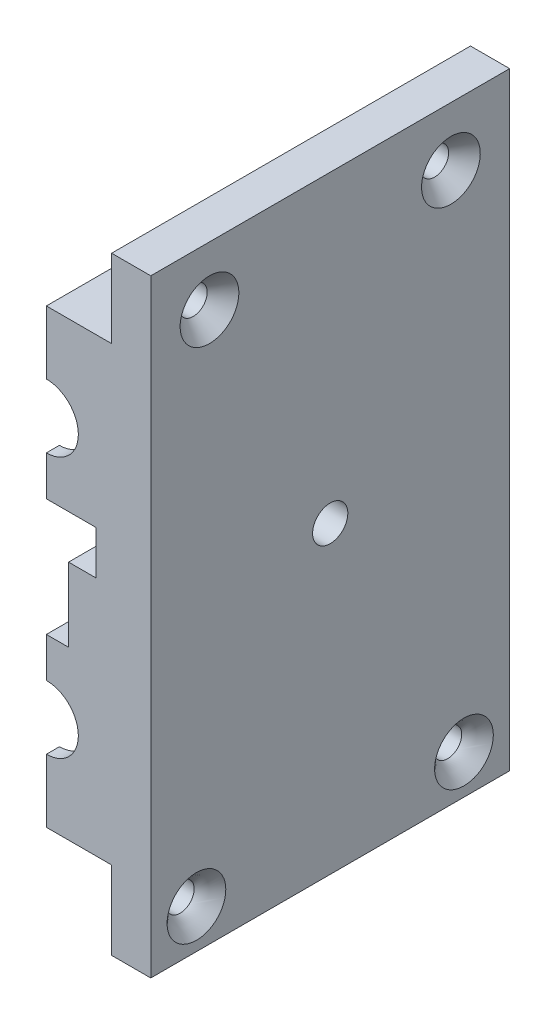
SolidWorks part; units mm, degrees
ref_plane "Front Plane" through (0, 0, 0) normal (0, 0, 1) x (1, 0, 0)
ref_plane "Top Plane" through (0, 0, 0) normal (0, 1, 0) x (1, 0, 0)
ref_plane "Right Plane" through (0, 0, 0) normal (1, 0, 0) x (0, 0, -1)
sketch "Sketch1" plane through (0, 0, 0) normal (0, 0, 1) x (1, 0, 0)
  line L0 (0, 0) -> (0, -93.2)
  line L1 (0, -93.2) -> (-6, -93.2)
  line L2 (-6, -93.2) -> (-6, -81.2)
  line L3 (-6, -81.2) -> (-16, -81.2)
  line L4 (-16, -81.2) -> (-16, -74.2)
  line L5 (-16, -59) -> (-16, -44.3)
  line L6 (-16, -44.3) -> (-8.4, -44.3)
  line L7 (-8.4, -44.3) -> (-8.4, -37.6)
  line L8 (-8.4, -37.6) -> (-16, -37.6)
  line L9 (-16, -37.6) -> (-16, -34.2)
  line L10 (-16, -19) -> (-16, -12)
  line L11 (-16, -12) -> (-6, -12)
  line L12 (-6, -12) -> (-6, 0)
  line L13 (-6, 0) -> (0, 0)
  arc A0 (-16, -74.2) -> (-16, -59) centre (-16, -66.6) ccw
  arc A1 (-16, -34.2) -> (-16, -19) centre (-16, -26.6) ccw
  dimension "D6" = 7.6
  dimension "D7" = 7.6
  dimension "D1" = 6
  dimension "D2" = 12
  dimension "D3" = 12
  dimension "D4" = 14.7
  dimension "D5" = 40
  dimension "D8" = 7
  dimension "D9" = 3.4
  dimension "D11" = 10
  dimension "D12" = 10
extrude "Boss-Extrude1" add sketch "Sketch1" along normal blind 55
ref_plane "Plane1" through (0, 0, 28.5) normal (0, 0, -1) x (-1, 0, 0)
sketch "Sketch2" plane through (0, 0, 28.5) normal (0, 0, -1) x (-1, 0, 0)
  line L0 (16, -34.2) -> (16, -31.5)
  line L1 (16, -21.7) -> (16, -19)
  arc A0 (16, -19) -> (16, -34.2) centre (16, -26.6) ccw
  arc A1 (16, -21.7) -> (16, -31.5) centre (16, -26.6) ccw
  dimension "D1" = 4.9
extrude "Boss-Extrude2" add sketch "Sketch2" along normal blind 2
sketch "Sketch3" plane through (0, 0, 28.5) normal (0, 0, -1) x (-1, 0, 0)
  line L0 (16, -74.2) -> (16, -71.5)
  line L1 (16, -61.7) -> (16, -59)
  arc A0 (16, -59) -> (16, -74.2) centre (16, -66.6) ccw
  arc A1 (16, -61.7) -> (16, -71.5) centre (16, -66.6) ccw
  dimension "D1" = 4.9
extrude "Boss-Extrude3" add sketch "Sketch3" along normal blind 2
ref_plane "Plane2" through (0, 0, 2) normal (0, 0, -1) x (-1, 0, 0)
sketch "Sketch4" plane through (0, 0, 2) normal (0, 0, -1) x (-1, 0, 0)
  line L1 (16, -59) -> (16, -61.7)
  line L2 (16, -74.2) -> (16, -81.2) construction
  line L4 (16, -71.5) -> (16, -74.2)
  line L5 (16, -19) -> (16, -21.7)
  line L6 (16, -31.5) -> (16, -34.2)
  arc A1 (16, -59) -> (16, -74.2) centre (16, -66.6) ccw construction
  arc A2 (16, -74.2) -> (16, -59) centre (16, -66.6) cw
  arc A4 (16, -61.7) -> (16, -71.5) centre (16, -66.6) ccw
  arc A5 (16, -34.2) -> (16, -19) centre (16, -26.6) cw
  arc A6 (16, -21.7) -> (16, -31.5) centre (16, -26.6) ccw
  dimension "D1" = 4.9
  dimension "D2" = 4.9
extrude "Boss-Extrude5" add sketch "Sketch4" along normal blind 2
ref_plane "Plane3" through (0, 0, 53) normal (0, 0, -1) x (-1, 0, 0)
sketch "Sketch5" plane through (0, 0, 53) normal (0, 0, -1) x (-1, 0, 0)
  line L0 (16, -19) -> (16, -21.7)
  line L1 (16, -31.5) -> (16, -34.2)
  line L2 (16, -59) -> (16, -61.7)
  line L3 (16, -71.5) -> (16, -74.2)
  arc A0 (16, -19) -> (16, -34.2) centre (16, -26.6) ccw construction
  arc A1 (16, -34.2) -> (16, -19) centre (16, -26.6) cw
  arc A2 (16, -21.7) -> (16, -31.5) centre (16, -26.6) ccw
  arc A3 (16, -74.2) -> (16, -59) centre (16, -66.6) cw
  arc A4 (16, -61.7) -> (16, -71.5) centre (16, -66.6) ccw
  dimension "D1" = 4.9
extrude "Boss-Extrude6" add sketch "Sketch5" against normal blind 2
sketch "Sketch7" plane through (0, 0, 55) normal (0, 0, 1) x (1, 0, 0)
  line L1 (-16, -44.3) -> (-12.6, -44.3)
  line L2 (-16, -44.3) -> (-16, -55.6)
  line L3 (-16, -55.6) -> (-12.6, -55.6)
  line L4 (-12.6, -44.3) -> (-12.6, -55.6)
  dimension "D1" = 3.4
  dimension "D2" = 11.3
extrude "Cut-Extrude2" cut sketch "Sketch7" against normal up to surface (55 mm away) up to face at (-9.9375, -45.1875, 0)
sketch "Sketch8" plane through (0, 0, 0) normal (1, 0, 0) x (0, 0, -1)
  line L0 (-55, -93.2) -> (-55, 0) construction
  line L1 (0, -93.2) -> (0, 0) construction
  line L2 (-55, 0) -> (0, 0) construction
  line L3 (-55, -93.2) -> (0, -93.2) construction
  circle A0 centre (-46, -9) radius 2.15
  circle A1 centre (-9, -9) radius 2.15
  circle A2 centre (-7, -87.2) radius 2.15
  circle A3 centre (-48, -87.2) radius 2.15
  dimension "D1" = 4.3
  dimension "D2" = 4.3
  dimension "D3" = 4.3
  dimension "D4" = 4.3
  dimension "D5" = 9
  dimension "D6" = 9
  dimension "D7" = 7
  dimension "D8" = 7
  dimension "D9" = 9
  dimension "D10" = 9
  dimension "D11" = 6
  dimension "D12" = 6
extrude "Cut-Extrude3" cut sketch "Sketch8" against normal up to surface (6 mm away) up to face at (-6, -6, 27.5)
sketch "Sketch9" plane through (0, 0, 0) normal (1, 0, 0) x (0, 0, -1)
  line L0 (-55, 0) -> (0, 0) construction
  line L1 (-55, -93.2) -> (-55, 0) construction
  circle A0 centre (-27.5, -46.6) radius 2.7
  dimension "D1" = 5.4
  dimension "D2" = 46.6
  dimension "D3" = 27.5
extrude "Cut-Extrude4" cut sketch "Sketch9" against normal up to surface (12.6 mm away) up to face at (-12.6, -49.95, 27.5)
ref_plane "Plane4" through (-2.5, 0, 0) normal (1, 0, 0) x (0, 0, -1)
sketch "Sketch12" plane through (-2.5, 0, 0) normal (1, 0, 0) x (0, 0, -1)
  circle A0 centre (-46, -9) radius 2.15 construction
  circle A1 centre (-46, -9) radius 2.15
sketch "Sketch13" plane through (0, 0, 0) normal (1, 0, 0) x (0, 0, -1)
  circle A0 centre (-46, -9) radius 4.5
  dimension "D1" = 9
loft "Cut-Loft1" cut profiles "Sketch13", "Sketch12" connector at (0, -9.4432, 50.4781) connector at (-2.5, -8.8852, 48.1469)
pattern_linear "LPattern1" count 2 spacing 37 along (0, 0, -1) of "Cut-Loft1"
sketch "Sketch14" plane through (-2.5, 0, 0) normal (1, 0, 0) x (0, 0, -1)
  circle A0 centre (-48, -87.2) radius 2.15 construction
  circle A1 centre (-48, -87.2) radius 2.15
sketch "Sketch15" plane through (0, 0, 0) normal (1, 0, 0) x (0, 0, -1)
  circle A0 centre (-48, -87.2) radius 4.5
  dimension "D1" = 9
loft "Cut-Loft2" cut profiles "Sketch14", "Sketch15" connector at (-2.5, -88.8038, 46.5681) connector at (0, -88.245, 43.623)
pattern_linear "LPattern2" count 2 spacing 41 along (0, 0, -1) of "Cut-Loft2"
